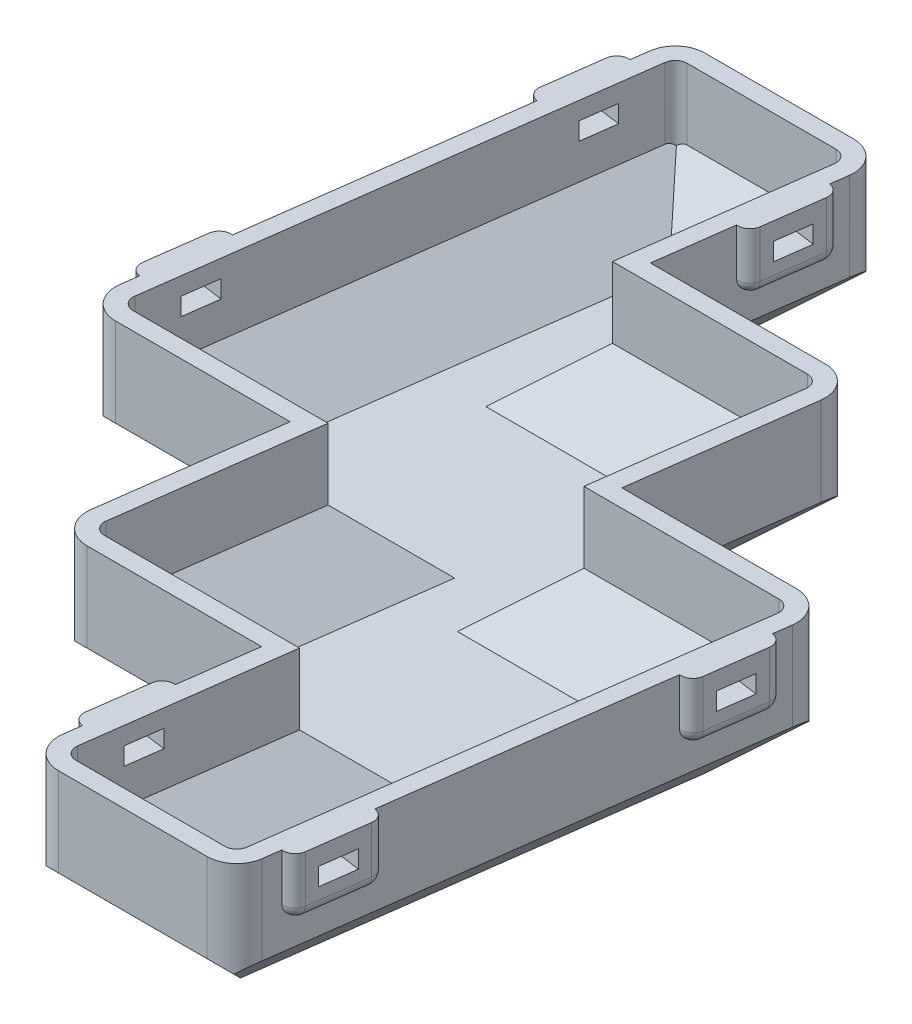
SolidWorks part; units mm, degrees
ref_plane "Front Plane" through (0, 0, 0) normal (0, 0, 1) x (1, 0, 0)
ref_plane "Top Plane" through (0, 0, 0) normal (0, 1, 0) x (1, 0, 0)
ref_plane "Right Plane" through (0, 0, 0) normal (1, 0, 0) x (0, 0, -1)
sketch "Sketch1" plane through (0, 0, 0) normal (0, 1, 0) x (1, 0, 0)
  line L12 (-11.6707, 44.6001) -> (23.6432, 44.6001)
  line L17 (-11.6707, 44.6001) -> (-23.6432, -44.6001)
  line L18 (23.6432, 44.6001) -> (11.6707, -44.6001)
  line L19 (-23.6432, -44.6001) -> (11.6707, -44.6001)
  line L20 (5.9862, 44.6001) -> (-5.9862, -44.6001) construction
  line L21 (42.2332, -80) -> (6.9193, -80)
  line L22 (42.2332, -80) -> (54.2056, 9.2001)
  line L23 (6.9193, -80) -> (18.8918, 9.2001)
  line L24 (54.2056, 9.2001) -> (18.8918, 9.2001)
  line L25 (24.5762, -80) -> (36.5487, 9.2001) construction
  line L26 (-42.2332, 80) -> (-6.9193, 80)
  line L27 (-42.2332, 80) -> (-54.2056, -9.2001)
  line L28 (-6.9193, 80) -> (-18.8918, -9.2001)
  line L29 (-54.2056, -9.2001) -> (-18.8918, -9.2001)
  line L30 (-24.5762, 80) -> (-36.5487, -9.2001) construction
  line L31 (-20.2136, -41.6001) -> (9.0465, -41.6001) construction
  line L32 (-20.2136, -41.6001) -> (-9.0465, 41.6001) construction
  line L33 (9.0465, -41.6001) -> (20.2136, 41.6001)
  line L34 (-9.0465, 41.6001) -> (20.2136, 41.6001) construction
  line L35 (5.5836, 41.6001) -> (19.9547, 39.6712) construction
  line L36 (-18.8918, -9.2001) -> (18.8918, 9.2001) construction
  point P7 (0, 0)
  point P20 (5.5836, 41.6001)
  point P21 (-5.5836, -41.6001)
  point P26 (14.63, 0)
  point P28 (0, 0)
  point P31 (20.0024, 17.4744)
  dimension "D1" = 90
  dimension "D2" = 29
  dimension "D3" = 82
  dimension "D4" = 3
  dimension "D5" = 3
  dimension "D6" = 160
extrude "Boss-Extrude1" add sketch "Sketch1" along normal blind 25 contours L18 | L17 L18 | L17 region at (0, 0, 0) region at (-30.5625, 0, -35.3999) region at (30.5625, 0, 35.3999)
sketch "Sketch4" plane through (0, 25, 0) normal (0, 1, 0) x (1, 0, 0)
  line L0 (-20.2136, -41.6001) -> (9.0465, -41.6001)
  line L1 (-20.2136, -41.6001) -> (-9.0465, 41.6001)
  line L2 (9.0465, -41.6001) -> (20.2136, 41.6001)
  line L3 (-9.0465, 41.6001) -> (20.2136, 41.6001)
  line L4 (10.3489, -77) -> (39.6089, -77)
  line L5 (10.3489, -77) -> (21.516, 6.2001)
  line L6 (39.6089, -77) -> (50.7761, 6.2001)
  line L7 (21.516, 6.2001) -> (50.7761, 6.2001)
  line L8 (36.146, 6.2001) -> (24.9789, -77) construction
  line L9 (-39.6089, 77) -> (-10.3489, 77)
  line L10 (-39.6089, 77) -> (-50.7761, -6.2001)
  line L11 (-10.3489, 77) -> (-21.516, -6.2001)
  line L12 (-50.7761, -6.2001) -> (-21.516, -6.2001)
  line L13 (-24.9789, 77) -> (-36.146, -6.2001) construction
  line L14 (-42.2332, 80) -> (-6.9193, 80) construction
  line L15 (-42.2332, 80) -> (-54.2056, -9.2001) construction
  line L16 (54.2056, 9.2001) -> (18.8918, 9.2001) construction
  line L17 (6.9193, -80) -> (18.8918, 9.2001) construction
  line L18 (-10.3489, 77) -> (-4.2951, 77)
  line L19 (-20.2136, -41.6001) -> (-26.2674, -41.6001)
  line L20 (10.3489, -77) -> (4.2951, -77)
  line L21 (20.2136, 41.6001) -> (26.2674, 41.6001)
  line L22 (-9.0465, 41.6001) -> (-15.1003, 41.6001)
  line L23 (-21.516, -6.2001) -> (-15.4622, -6.2001)
  line L24 (9.0465, -41.6001) -> (15.1003, -41.6001)
  line L25 (21.516, 6.2001) -> (15.4622, 6.2001)
  dimension "D1" = 3
  dimension "D2" = 3
  dimension "D3" = 3
  dimension "D4" = 3
extrude "Cut-Extrude1" cut sketch "Sketch4" against normal blind 22 contours L10 L12 L11 L9 | L19 L1 L18 L11 | L3 L1 L0 L2 | L7 L5 L4 L6 | L21 L2 L20 L5 region at (0, 25, 0) region at (15.2812, 25, 17.7) region at (-15.2812, 25, -17.7) region at (30.5625, 25, 35.3999) region at (-30.5625, 25, -35.3999)
chamfer "Chamfer2" distance 10 angle 45 24 edges at (36.5487, 0, -9.2001) (21.2675, 0, -26.9001) (5.9862, 0, -44.6001) (-9.295, 0, -62.3) (-24.5762, 0, -80) (-48.2194, 0, -35.3999) (-36.5487, 0, 9.2001) (-21.2675, 0, 26.9001) (-5.9862, 0, 44.6001) (9.295, 0, 62.3) (24.5762, 0, 80) (48.2194, 0, 35.3999) (-24.9789, 3, -77) (-12.7246, 3, -59.3) (2.5567, 3, -41.6001) (17.8379, 3, -23.9001) (33.1191, 3, -6.2001) (45.1925, 3, 35.3999) (24.9789, 3, 77) (12.7246, 3, 59.3) (-2.5567, 3, 41.6001) (-17.8379, 3, 23.9001) (-33.1191, 3, 6.2001) (-45.1925, 3, -35.3999)
fillet "Fillet4" radius 5 8 edges at (42.2332, 17.5, 80) (6.9193, 17.5, 80) (-23.6432, 17.5, 44.6001) (-54.2056, 17.5, 9.2001) (-42.2332, 17.5, -80) (-6.9193, 17.5, -80) (23.6432, 17.5, -44.6001) (54.2056, 17.5, -9.2001)
fillet "Fillet5" radius 2 8 edges at (-10.3489, 19, -77) (10.3489, 19, 77) (39.6089, 19, 77) (50.7761, 19, -6.2001) (20.2136, 19, -41.6001) (-20.2136, 19, 41.6001) (-50.7761, 19, 6.2001) (-39.6089, 19, -77)
sketch "Sketch13" plane through (52.0334, 0, 6.9839) normal (0.9911, 0, 0.133) x (0.133, 0, -0.9911)
  line L0 (-69.2971, 25) -> (10.6132, 25) construction
  line L1 (-52.2971, 15) -> (-66.2971, 15)
  line L2 (-52.2971, 15) -> (-52.2971, 25)
  line L3 (-52.2971, 25) -> (-66.2971, 25)
  line L4 (-66.2971, 15) -> (-66.2971, 25)
  line L5 (-52.2971, 15) -> (-66.2971, 25) construction
  line L6 (-52.2971, 25) -> (-66.2971, 15) construction
  line L7 (-69.2971, 25) -> (-69.2971, 10) construction
  line L8 (-29.3419, 25) -> (-29.3419, 10) construction
  line L9 (-69.2971, 10) -> (10.6132, 10) construction
  line L10 (-6.3868, 25) -> (7.6132, 15) construction
  line L11 (-6.3868, 15) -> (7.6132, 25) construction
  line L12 (7.6132, 15) -> (7.6132, 25)
  line L13 (-6.3868, 25) -> (7.6132, 25)
  line L14 (-6.3868, 15) -> (-6.3868, 25)
  line L15 (-6.3868, 15) -> (7.6132, 15)
  point P0 (-59.2971, 20)
  point P17 (0.6132, 20)
  dimension "D1" = 3
  dimension "D2" = 10
  dimension "D3" = 14
extrude "Boss-Extrude7" add sketch "Sketch13" along normal blind 2
sketch "Sketch14" plane through (-52.0334, 0, -6.9839) normal (-0.9911, 0, -0.133) x (-0.133, 0, 0.9911)
  line L0 (-69.2971, 25) -> (10.6132, 25) construction
  line L5 (-52.2971, 15) -> (-66.2971, 15)
  line L6 (-52.2971, 15) -> (-52.2971, 25)
  line L7 (-52.2971, 25) -> (-66.2971, 25)
  line L8 (-66.2971, 15) -> (-66.2971, 25)
  line L9 (-52.2971, 15) -> (-66.2971, 25) construction
  line L10 (-52.2971, 25) -> (-66.2971, 15) construction
  line L11 (-69.2971, 25) -> (-69.2971, 10) construction
  line L12 (-29.3419, 25) -> (-29.3419, 10) construction
  line L13 (-69.2971, 10) -> (10.6132, 10) construction
  line L14 (-6.3868, 25) -> (7.6132, 15) construction
  line L15 (-6.3868, 15) -> (7.6132, 25) construction
  line L16 (7.6132, 15) -> (7.6132, 25)
  line L17 (-6.3868, 25) -> (7.6132, 25)
  line L18 (-6.3868, 15) -> (-6.3868, 25)
  line L19 (-6.3868, 15) -> (7.6132, 15)
  point P0 (-59.2971, 20)
  point P17 (0.6132, 20)
  dimension "D1" = 3
  dimension "D2" = 14
  dimension "D3" = 10
extrude "Boss-Extrude8" add sketch "Sketch14" along normal blind 2
sketch "Sketch15" plane through (17.3445, 0, 2.328) normal (-0.9911, 0, -0.133) x (-0.133, 0, 0.9911)
  line L0 (42.6511, 25) -> (72.6526, 25) construction
  line L1 (69.6526, 15) -> (55.6526, 15)
  line L2 (69.6526, 15) -> (69.6526, 25)
  line L3 (69.6526, 25) -> (55.6526, 25)
  line L4 (55.6526, 15) -> (55.6526, 25)
  line L5 (69.6526, 15) -> (55.6526, 25) construction
  line L6 (69.6526, 25) -> (55.6526, 15) construction
  line L7 (72.6526, 10) -> (72.6526, 25) construction
  point P0 (62.6526, 20)
  dimension "D1" = 10
  dimension "D2" = 14
  dimension "D3" = 3
extrude "Boss-Extrude9" add sketch "Sketch15" along normal blind 2
sketch "Sketch16" plane through (-17.3445, 0, -2.328) normal (0.9911, 0, 0.133) x (0.133, 0, -0.9911)
  line L0 (72.6526, 25) -> (42.6511, 25) construction
  line L1 (69.6526, 15) -> (55.6526, 15)
  line L2 (69.6526, 15) -> (69.6526, 25)
  line L3 (69.6526, 25) -> (55.6526, 25)
  line L4 (55.6526, 15) -> (55.6526, 25)
  line L5 (69.6526, 15) -> (55.6526, 25) construction
  line L6 (69.6526, 25) -> (55.6526, 15) construction
  line L7 (72.6526, 10) -> (72.6526, 25) construction
  point P0 (62.6526, 20)
  dimension "D1" = 3
  dimension "D2" = 14
  dimension "D3" = 10
extrude "Boss-Extrude10" add sketch "Sketch16" along normal blind 2
sketch "Sketch17" plane through (54.0156, 0, 7.25) normal (0.9911, 0, 0.133) x (0.133, 0, -0.9911)
  line L0 (-52.2971, 25) -> (-66.2971, 25) construction
  line L1 (-56.2971, 19) -> (-62.2971, 19)
  line L2 (-56.2971, 19) -> (-56.2971, 22)
  line L3 (-56.2971, 22) -> (-62.2971, 22)
  line L4 (-62.2971, 19) -> (-62.2971, 22)
  line L5 (-56.2971, 19) -> (-62.2971, 22) construction
  line L6 (-56.2971, 22) -> (-62.2971, 19) construction
  line L7 (-66.2971, 25) -> (-66.2971, 15) construction
  line L8 (-29.3419, 25) -> (-29.3419, 10) construction
  line L9 (-52.2971, 25) -> (-6.3868, 25) construction
  line L10 (-69.2971, 10) -> (10.6132, 10) construction
  line L11 (-2.3868, 22) -> (3.6132, 19) construction
  line L12 (-2.3868, 19) -> (3.6132, 22) construction
  line L13 (3.6132, 19) -> (3.6132, 22)
  line L14 (-2.3868, 22) -> (3.6132, 22)
  line L15 (-2.3868, 19) -> (-2.3868, 22)
  line L16 (-2.3868, 19) -> (3.6132, 19)
  point P0 (-59.2971, 20.5)
  point P19 (0.6132, 20.5)
  dimension "D1" = 3
  dimension "D2" = 4
  dimension "D3" = 6
  dimension "D4" = 3
extrude "Cut-Extrude6" cut sketch "Sketch17" against normal up to surface (5 mm away) up to face at (45.1568, 19, 35.666)
sketch "Sketch18" plane through (-54.0156, 0, -7.25) normal (-0.9911, 0, -0.133) x (-0.133, 0, 0.9911)
  line L0 (-56.2971, 19) -> (-62.2971, 19)
  line L1 (-56.2971, 19) -> (-56.2971, 22)
  line L2 (-56.2971, 22) -> (-62.2971, 22)
  line L3 (-62.2971, 19) -> (-62.2971, 22)
  line L4 (-56.2971, 19) -> (-62.2971, 22) construction
  line L5 (-56.2971, 22) -> (-62.2971, 19) construction
  line L6 (-29.3419, 25) -> (-29.3419, 9.8874) construction
  line L7 (-2.3868, 22) -> (3.6132, 19) construction
  line L8 (-2.3868, 19) -> (3.6132, 22) construction
  line L9 (3.6132, 19) -> (3.6132, 22)
  line L10 (-2.3868, 22) -> (3.6132, 22)
  line L11 (-2.3868, 19) -> (-2.3868, 22)
  line L12 (-2.3868, 19) -> (3.6132, 19)
  line L13 (-66.2971, 25) -> (-66.2971, 15) construction
  line L14 (-52.2971, 25) -> (-66.2971, 25) construction
  line L15 (-52.2971, 25) -> (-6.3868, 25) construction
  point P0 (-59.2971, 20.5)
  point P11 (0.6132, 20.5)
  point P16 (-29.3419, 25)
  dimension "D1" = 6
  dimension "D2" = 3
  dimension "D3" = 4
  dimension "D4" = 3
extrude "Cut-Extrude7" cut sketch "Sketch18" against normal up to surface (5 mm away) up to face at (-45.1568, 19, -35.666)
sketch "Sketch19" plane through (-15.3622, 0, -2.0619) normal (0.9911, 0, 0.133) x (0.133, 0, -0.9911)
  line L0 (69.6526, 25) -> (55.6526, 25) construction
  line L1 (65.6526, 19) -> (59.6526, 19)
  line L2 (65.6526, 19) -> (65.6526, 22)
  line L3 (65.6526, 22) -> (59.6526, 22)
  line L4 (59.6526, 19) -> (59.6526, 22)
  line L5 (65.6526, 19) -> (59.6526, 22) construction
  line L6 (65.6526, 22) -> (59.6526, 19) construction
  line L7 (69.6526, 15) -> (69.6526, 25) construction
  point P0 (62.6526, 20.5)
  dimension "D1" = 3
  dimension "D2" = 6
  dimension "D3" = 3
  dimension "D4" = 4
extrude "Cut-Extrude8" cut sketch "Sketch19" against normal up to surface (5 mm away) up to face at (-12.8766, 19, -58.167)
sketch "Sketch20" plane through (15.3622, 0, 2.0619) normal (-0.9911, 0, -0.133) x (-0.133, 0, 0.9911)
  line L0 (69.6526, 15) -> (69.6526, 25) construction
  line L1 (65.6526, 19) -> (59.6526, 19)
  line L2 (65.6526, 19) -> (65.6526, 22)
  line L3 (65.6526, 22) -> (59.6526, 22)
  line L4 (59.6526, 19) -> (59.6526, 22)
  line L5 (65.6526, 19) -> (59.6526, 22) construction
  line L6 (65.6526, 22) -> (59.6526, 19) construction
  line L7 (69.6526, 25) -> (55.6526, 25) construction
  point P0 (62.6526, 20.5)
  dimension "D1" = 4
  dimension "D2" = 3
  dimension "D3" = 6
  dimension "D4" = 3
extrude "Cut-Extrude9" cut sketch "Sketch20" against normal up to surface (5 mm away) up to face at (12.8766, 19, 58.167)
fillet "Fillet6" radius 2 18 edges at (-55.0284, 20, 0.2956) (-54.0972, 15, -6.6422) (-53.166, 20, -13.58) (-47.0587, 20, -59.0823) (-46.1275, 15, -66.0201) (-45.1963, 20, -72.9579) (6.0965, 20, 71.0955) (7.0277, 15, 64.1577) (7.9589, 20, 57.2199) (45.1963, 20, 72.9579) (46.1275, 15, 66.0201) (47.0587, 20, 59.0823) (53.166, 20, 13.58) (54.0972, 15, 6.6422) (55.0284, 20, -0.2956) (-7.9589, 20, -57.2199) (-7.0277, 15, -64.1577) (-6.0965, 20, -71.0955)
